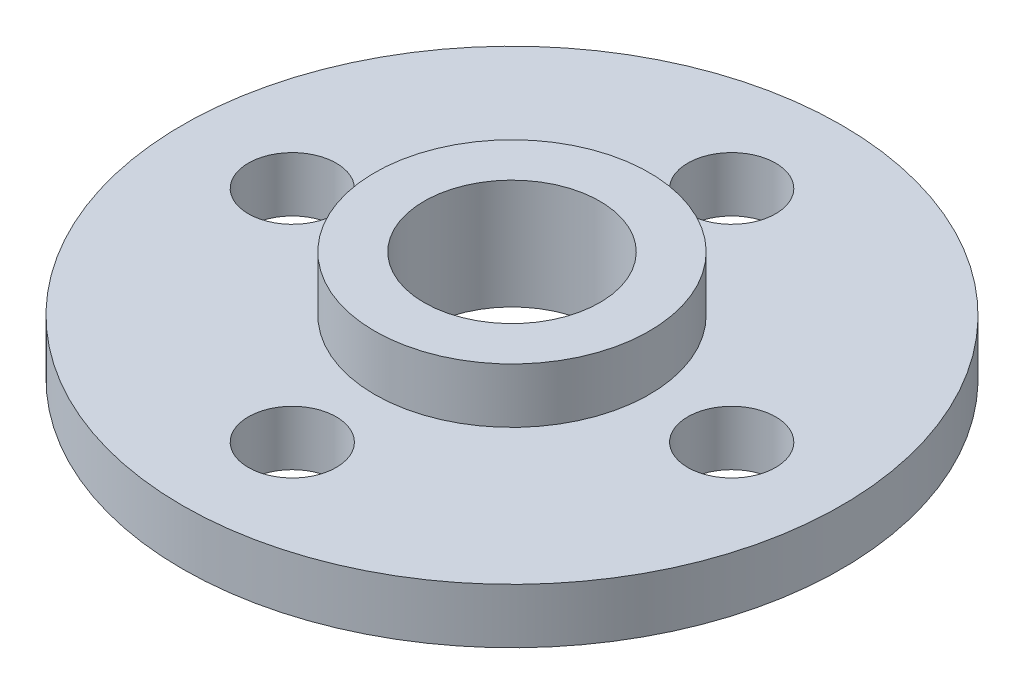
SolidWorks part; units mm, degrees
ref_plane "Front Plane" through (0, 0, 0) normal (0, 0, 1) x (1, 0, 0)
ref_plane "Top Plane" through (0, 0, 0) normal (0, 1, 0) x (1, 0, 0)
ref_plane "Right Plane" through (0, 0, 0) normal (1, 0, 0) x (0, 0, -1)
sketch "Sketch1" plane through (0, 0, 0) normal (0, 1, 0) x (1, 0, 0)
  circle A0 centre (0, 0) radius 30
  circle A1 centre (0, 20) radius 4
  circle A2 centre (0, 0) radius 8
  circle A3 centre (20, 0) radius 4
  circle A4 centre (0, -20) radius 4
  circle A5 centre (-20, 0) radius 4
  circle A6 centre (0, 0) radius 12.5
  point P15 (0, 0)
  dimension "D1" = 60
  dimension "D3" = 8
  dimension "D4" = 16
  dimension "D5" = 4
  dimension "D6" = 25
  dimension "D2" = 20
extrude "Boss-Extrude1" add sketch "Sketch1" along normal blind 5 contours A6 | A4 | A3 | A1 | A5 | A0
extrude "Boss-Extrude2" add sketch "Sketch1<6>" along normal blind 10 contours A6 | A2
sketch "Sketch1<6>" plane through (0, 0, 0) normal (0, 1, 0) x (1, 0, 0) same geometry as "Sketch1"
